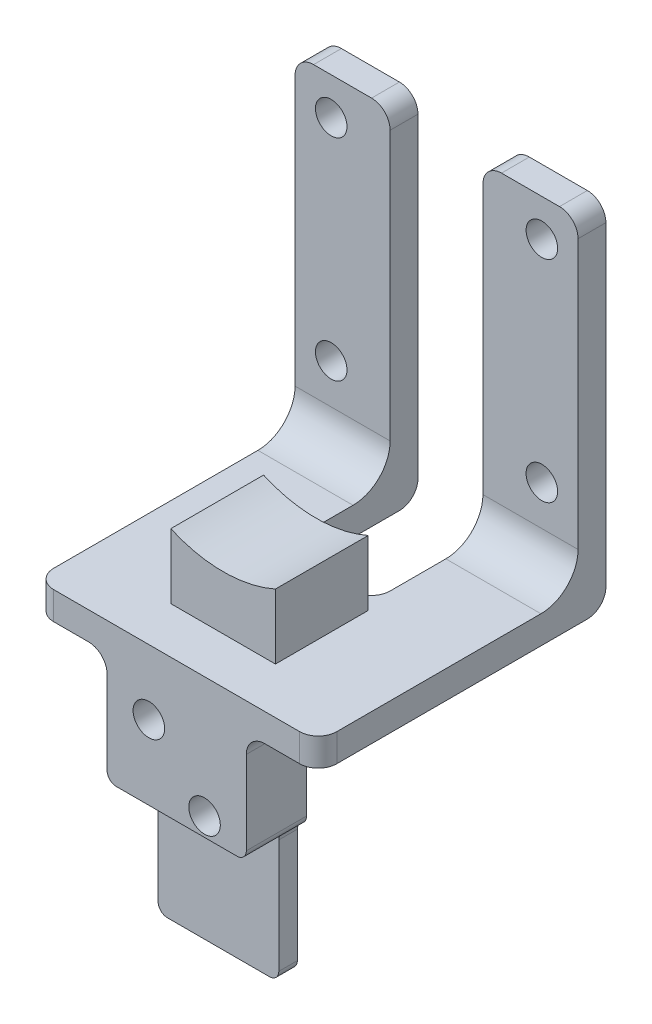
SolidWorks part; units mm, degrees
ref_plane "Front Plane" through (0, 0, 0) normal (0, 0, 1) x (1, 0, 0)
ref_plane "Top Plane" through (0, 0, 0) normal (0, 1, 0) x (1, 0, 0)
ref_plane "Right Plane" through (0, 0, 0) normal (1, 0, 0) x (0, 0, -1)
other "Center of Mass"
sketch "Sketch2" plane through (0, 0, 0) normal (0, 1, 0) x (1, 0, 0)
  line L1 (15.25, -14) -> (-15.25, -14)
  line L2 (15.25, -14) -> (15.25, 14)
  line L3 (15.25, 14) -> (-15.25, 14)
  line L4 (-15.25, -14) -> (-15.25, 14)
  line L5 (15.25, -14) -> (-15.25, 14) construction
  line L6 (15.25, 14) -> (-15.25, -14) construction
  line L7 (-5, 14) -> (5, 14)
  line L8 (-5, 14) -> (-5, 2)
  line L9 (-5, 2) -> (5, 2)
  line L10 (5, 14) -> (5, 2)
  point P0 (0, 0)
  point P10 (0, 2)
  dimension "D1" = 30.5
  dimension "D2" = 10
  dimension "D3" = 12
  dimension "D4" = 28
extrude "Boss-Extrude1" add sketch "Sketch2" along normal blind 3 contours L3 L10 L9 L8 L4 L1 L2 region at (0, 0, 1.3079)
sketch "Sketch3" plane through (0, 3, 0) normal (0, 1, 0) x (1, 0, 0)
  line L1 (-15.25, 14) -> (-5, 14)
  line L2 (-15.25, 14) -> (-15.25, 17)
  line L3 (-15.25, 17) -> (-5, 17)
  line L4 (-5, 14) -> (-5, 17)
  line L5 (-5, 14) -> (-5, 2) construction
  line L6 (0, -1.65) -> (0, 1.65) construction
  line L7 (15.25, 17) -> (5, 17)
  line L8 (5, 14) -> (5, 17)
  line L9 (15.25, 14) -> (5, 14)
  line L10 (15.25, 14) -> (15.25, 17)
  dimension "D1" = 3
extrude "Boss-Extrude2" add sketch "Sketch3" against normal up to surface (3 mm away) and the other way blind 35 up to face at (0, 0, -4)
sketch "Sketch4" plane through (0, 0, 0) normal (0, -1, 0) x (1, 0, 0)
  line L0 (15.25, 14) -> (-15.25, 14) construction
  line L1 (-7.5, 14) -> (7.5, 14)
  line L2 (-7.5, 14) -> (-7.5, 7.5)
  line L3 (-7.5, 7.5) -> (7.5, 7.5)
  line L4 (7.5, 14) -> (7.5, 7.5)
  point P6 (0, 7.5)
  dimension "D1" = 6.5
  dimension "D2" = 15
extrude "Boss-Extrude3" add sketch "Sketch4" along normal blind 12
sketch "Sketch5" plane through (0, 0, 14) normal (0, 0, 1) x (1, 0, 0)
  point P0 (-3, -4)
  point P1 (3, -10)
hole_wizard "M3 Clearance Hole1" positions "Sketch6" profile "Sketch7" hole size "M3" standard "ANSI Metric" end condition through all
sketch "Sketch6" plane through (0, 0, 14) normal (0, 0, 1) x (1, 0, 0)
  point P0 (-3, -4)
  point P3 (3, -10)
sketch "Sketch7" plane through (-3, -4, 14) normal (1, 0, 0) x (0, -1, 0)
  line L0 (0, 0) -> (0, 31)
  line L1 (0, 31) -> (1.7, 31)
  line L2 (1.7, 31) -> (1.7, 0)
  line L5 (1.7, 0) -> (0, 0)
  line L11 (0, -6.35) -> (0, 107.95) construction
  dimension "Thru Hole Dia." = 3.4
  dimension "Thru Hole Depth" = 31
sketch "Sketch8" plane through (0, 0, -14) normal (0, 0, 1) x (1, 0, 0)
  line L5 (-15.25, 38) -> (-5, 38) construction
  line L7 (11.3491, 34) -> (-11.3491, 34) construction
  point P0 (-11.3491, 34)
  point P1 (-11.3491, 11.3019)
  point P2 (11.3491, 11.3019)
  point P3 (11.3491, 34)
  point P28 (0, 34)
  dimension "D1" = 22.6981
  dimension "D2" = 22.6981
  dimension "D3" = 4
hole_wizard "M3 Clearance Hole2" positions "Sketch9" profile "Sketch10" hole size "M3" standard "ANSI Metric" end condition through all
sketch "Sketch9" plane through (0, 0, -14) normal (0, 0, 1) x (1, 0, 0)
  point P0 (-11.3491, 34)
  point P3 (11.3491, 34)
  point P6 (11.3491, 11.3019)
  point P9 (-11.3491, 11.3019)
sketch "Sketch10" plane through (-11.3491, 34, -14) normal (1, 0, 0) x (0, -1, 0)
  line L0 (0, 0) -> (0, 3)
  line L1 (0, 3) -> (1.7, 3)
  line L2 (1.7, 3) -> (1.7, 0)
  line L5 (1.7, 0) -> (0, 0)
  line L11 (0, -6.35) -> (0, 107.95) construction
  dimension "Thru Hole Dia." = 3.4
  dimension "Thru Hole Depth" = 3
fillet "Fillet1" radius 1 2 edges at (-7.5, -12, 10.75) (7.5, -12, 10.75)
fillet "Fillet2" radius 2 12 edges at (-15.25, 1.5, 14) (15.25, 1.5, 14) (-10.125, 0, -17) (10.125, 0, -17) (5, 1.5, -2) (-5, 1.5, -2) (7.5, 0, 10.75) (-7.5, 0, 10.75) (-15.25, 38, -15.5) (-5, 38, -15.5) (5, 38, -15.5) (15.25, 38, -15.5)
fillet "Fillet3" radius 1 1 edges at (0, 0, 7.5)
sketch "Sketch11" plane through (0, -12, 0) normal (0, -1, 0) x (1, 0, 0)
  line L0 (6.5, 7.5) -> (6.5, 14) construction
  line L1 (-6.5, 9.5) -> (6.5, 9.5)
  line L2 (-6.5, 9.5) -> (-6.5, 7.5)
  line L3 (-6.5, 7.5) -> (6.5, 7.5)
  line L4 (6.5, 9.5) -> (6.5, 7.5)
  line L5 (-6.5, 7.5) -> (6.5, 7.5) construction
  dimension "D1" = 2
extrude "Boss-Extrude4" add sketch "Sketch11" along normal blind 14
fillet "Fillet4" radius 1 4 edges at (-6.5, -26, 8.5) (6.5, -26, 8.5) (6.5, -12, 8.5) (-6.5, -12, 8.5)
fillet "Fillet5" radius 4 2 edges at (-10.125, 3, -14) (10.125, 3, -14)
sketch "Sketch13" plane through (0, 0, 14) normal (0, 0, 1) x (1, 0, 0)
  line L0 (-5.637, 3) -> (5.637, 3)
  line L1 (13.25, 3) -> (-13.25, 3) construction
  line L2 (5.637, 3) -> (5.637, 10)
  line L3 (-5.637, 10) -> (-5.637, 3)
  circle A0 centre (0, 22.6509) radius 13.85 construction
  arc A1 (-5.637, 10) -> (5.637, 10) centre (0, 22.6509) ccw
  point P4 (0, 3)
  line M3 (13.25, 3) -> (-13.25, 3)
  dimension "D1" = 13.85
  dimension "D2" = 7
extrude "Boss-Extrude5" add sketch "Sketch13" against normal blind 10 from offset 5 contours A1 L3 L2 M3 | A1 L2 L0 L3 region at (0, 6.1069, 14) offset against normal yes
